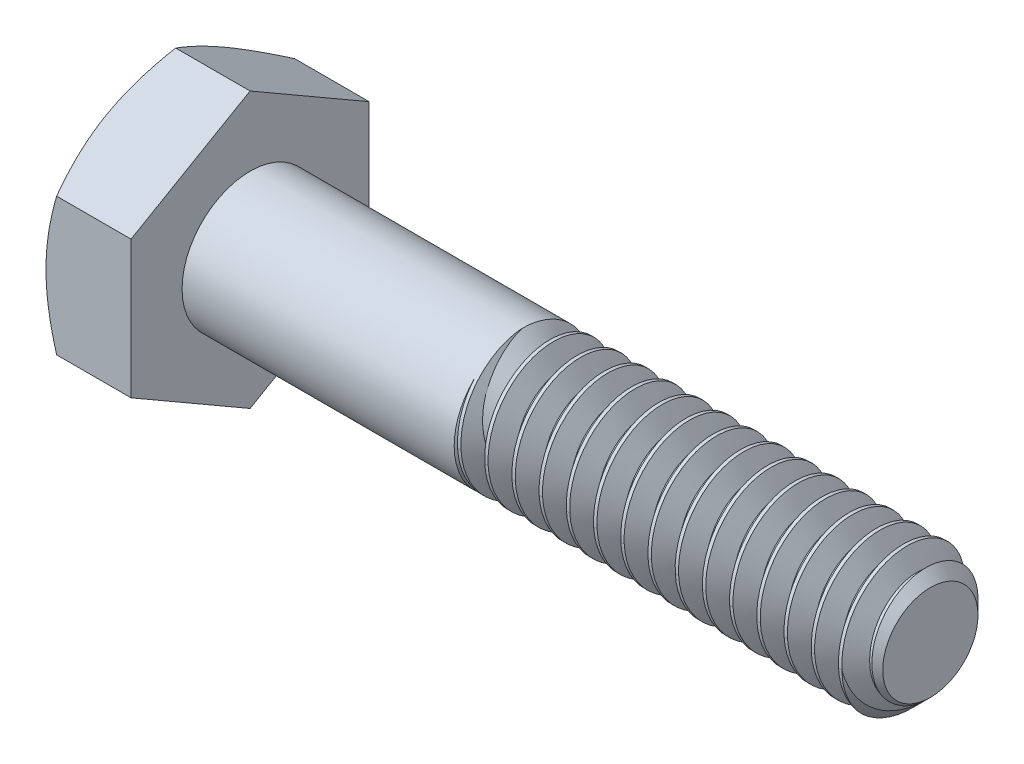
SolidWorks part; units mm, degrees
ref_plane "Front Plane" through (0, 0, 0) normal (0, 0, 1) x (1, 0, 0)
ref_plane "Top Plane" through (0, 0, 0) normal (0, 1, 0) x (1, 0, 0)
ref_plane "Right Plane" through (0, 0, 0) normal (1, 0, 0) x (0, 0, -1)
sketch "Sketch1" plane through (0, 0, 0) normal (0, 0, 1) x (1, 0, 0)
  line L0 (-17.8594, 0) -> (17.8594, 0) construction
  line L1 (17.8594, 3.175) -> (17.8594, -3.175) construction
  line L2 (-13.8906, 5.5562) -> (-13.8906, -5.5562) construction
  line L3 (-17.8594, 5.5562) -> (-17.8594, -5.5562) construction
  point P9 (-13.8906, 0)
  point P10 (13.4144, -3.175)
  dimension "Screw Dia" = 6.35
  dimension "Hex" = 11.1125
  dimension "Head Ht" = 3.9688
  dimension "Screw Lenght" = 31.75
  dimension "D1" = 4.445
ref_plane "Plane2" through (17.8594, 0, 0) normal (1, 0, 0) x (0, 0, -1)
sketch "Sketch5" plane through (17.8594, 0, 0) normal (1, 0, 0) x (0, 0, -1)
  circle A0 centre (0, 0) radius 3.175
extrude "Boss-Extrude3" add sketch "Sketch5" against normal up to vertex (31.75 mm away) up to point (-13.8906, 0, 0)
sketch "Sketch9" plane through (17.8594, 0, 0) normal (1, 0, 0) x (0, 0, -1)
  circle A1 centre (0, 0) radius 3.175
  circle A2 centre (0, 0) radius 3.175
  dimension "D1" = 0
curve "Helix/Spiral1" pitch 1.27 height 20.32 turns 16 parameters "Pitch"=1.27
chamfer "Chamfer1" distance 0.9525 angle 45 1 edges at (17.8594, 0, -3.175)
sketch "Sketch10" plane through (0, 0, 0) normal (0, 0, 1) x (1, 0, 0)
  line L0 (17.8594, 3.175) -> (18.3356, 2.3501)
  line L1 (18.3356, 2.3501) -> (18.4944, 2.3501)
  line L2 (18.4944, 2.3501) -> (18.9706, 3.175)
  line L3 (17.8594, 3.175) -> (18.9706, 3.175)
  line L4 (18.415, 3.175) -> (18.415, 2.3501) construction
  line L5 (18.0975, 2.7626) -> (18.7325, 2.7626) construction
  dimension "D1" = 60
  dimension "D2" = 0.1588
  dimension "D3" = 0.635
sweep "Cut-Sweep1" cut profiles "Sketch10" path "Helix/Spiral1" align with end faces yes
sketch "Sketch11" plane through (0, 0, 0) normal (0, 0, 1) x (1, 0, 0)
  line L0 (-13.8906, 3.175) -> (-13.8906, 0)
  line L1 (-13.8906, 0) -> (1.9844, 0)
  line L3 (1.9844, 0) -> (-1.1906, 3.175)
  line L4 (-13.8906, 3.175) -> (-1.1906, 3.175)
  dimension "D1" = 45
  dimension "MIn Thread" = 19.05
revolve "Revolve1" add sketch "Sketch11" angle 360 about L1
sketch "Sketch6" plane through (-13.8906, 0, 0) normal (-1, 0, 0) x (0, 0, 1)
  line L0 (0, 5.5562) -> (0, -5.5562) construction
  line L1 (5.5562, 3.2079) -> (0, 6.4158)
  line L2 (0, 6.4158) -> (-5.5562, 3.2079)
  line L3 (-5.5562, 3.2079) -> (-5.5562, -3.2079)
  line L4 (-5.5562, -3.2079) -> (0, -6.4158)
  line L5 (0, -6.4158) -> (5.5562, -3.2079)
  line L6 (5.5562, -3.2079) -> (5.5562, 3.2079)
  circle A0 centre (0, 0) radius 5.5562 construction
extrude "Boss-Extrude4" add sketch "Sketch6" along normal up to vertex (3.9688 mm away) up to point (-17.8594, -5.5562, 0)
sketch "Sketch7" plane through (-17.8594, 0, 0) normal (-1, 0, 0) x (0, 0, 1)
  circle A0 centre (0, 0) radius 5.5562 construction
  circle A1 centre (0, 0) radius 5.5562
sketch "Sketch8" plane through (-17.8594, 0, 0) normal (-1, 0, 0) x (0, 0, 1)
  circle A0 centre (0, 0) radius 5.5562 construction
  circle A1 centre (0, 0) radius 5.5562
extrude "Cut-Extrude3" cut sketch "Sketch8" against normal through all draft 60 flip side to cut
equation "\"D2@Sketch10\" = \"Pitch@Helix/Spiral1\"*.125"
equation "\"D3@Sketch10\" = \"Pitch@Helix/Spiral1\"*.5"
equation "\"D3@Helix/Spiral1\" = \"MIn Thread@Sketch11\"+\"Pitch@Helix/Spiral1\""
equation "\"D1@Chamfer1\" = \"Pitch@Helix/Spiral1\"*.75"
equation "\"D1@Sketch1\" = \"Pitch@Helix/Spiral1\"*3.5"
